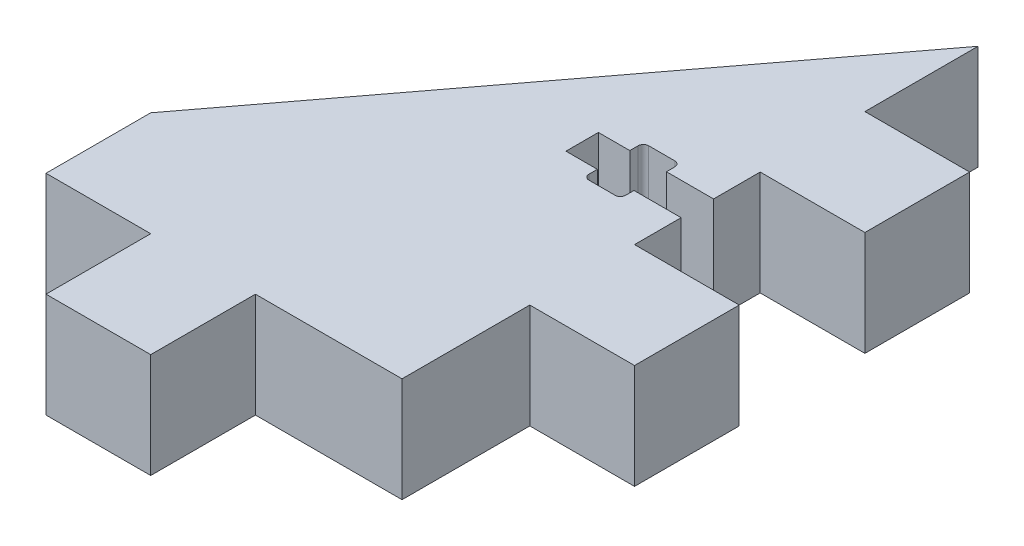
SolidWorks part; units mm, degrees
ref_plane "Front Plane" through (0, 0, 0) normal (0, 0, 1) x (1, 0, 0)
ref_plane "Top Plane" through (0, 0, 0) normal (0, 1, 0) x (1, 0, 0)
ref_plane "Right Plane" through (0, 0, 0) normal (1, 0, 0) x (0, 0, -1)
sketch "Sketch1" plane through (0, 0, 0) normal (0, 1, 0) x (1, 0, 0)
  line L0 (0, 0) -> (-14, 0)
  line L1 (-14, 0) -> (-14, -10)
  line L2 (-14, -10) -> (-24, -10)
  line L3 (-24, -10) -> (-24, 0)
  line L4 (-24, 0) -> (-34, 0)
  line L5 (-34, 0) -> (-34, 10)
  line L6 (-34, 10) -> (0, 55)
  line L7 (0, 55) -> (0, 44.2)
  line L8 (0, 44.2) -> (10, 44.2)
  line L9 (10, 44.2) -> (10, 34.2)
  line L10 (10, 34.2) -> (0, 34.2)
  line L11 (0, 34.2) -> (0, 22.2)
  line L12 (-24, 0) -> (-14, 0) construction
  line L13 (-19, 0) -> (-19, -10) construction
  line L14 (0, 17.2) -> (0, 12.2) construction
  line L15 (5, 12.2) -> (5, 21.2) construction
  line L16 (10, 34.2) -> (10, 22.2) construction
  line L17 (0, 28.2) -> (10, 28.2) construction
  line L24 (0, 22.2) -> (10, 22.2)
  line L25 (10, 22.2) -> (10, 12.2)
  line L26 (10, 12.2) -> (0, 12.2)
  line L27 (0, 12.2) -> (0, 0)
  line L32 (10, 39.2) -> (0, 39.2) construction
  line L33 (0, 39.2) -> (0, 34.2) construction
  line L34 (10, 17.2) -> (0, 17.2) construction
  line L35 (0, 17.2) -> (0, 22.2) construction
  dimension "D1" = 10
  dimension "D2" = 10
  dimension "D3" = 10
  dimension "D7" = 10
  dimension "D8" = 10
  dimension "D10" = 10
  dimension "D11" = 10
  dimension "D12" = 10
  dimension "D9" = 55
  dimension "D4" = 22
  dimension "D6" = 24
  dimension "D5" = 28.2
extrude "Boss-Extrude1" add sketch "Sketch1" along normal blind 10
sketch "Sketch2" [suppressed] plane through (0, 8, 0) normal (0, 1, 0) x (1, 0, 0)
  line L0 (0, 29.9) -> (0, 25.9) construction
  line L1 (0, 27.9) -> (-7.2, 27.9) construction
  line L2 (-7.2, 25.9) -> (-7.2, 29.9) construction
  line L3 (7.5, 36.4) -> (7.5, 20.4) construction
  line L4 (0, 36.4) -> (7.5, 36.4) construction
  line L5 (0, 27.9) -> (7.5, 27.9) construction
sketch "Sketch3" plane through (0, 10, 0) normal (0, 1, 0) x (1, 0, 0)
  line L0 (0, 28.2) -> (-11, 28.2) construction
  line L1 (0, 22.2) -> (0, 34.2) construction
  line L2 (-11, 29.75) -> (-8, 29.75)
  line L3 (-8, 29.75) -> (-8, 30.55)
  line L4 (-7.5, 31.05) -> (-5, 31.05)
  line L5 (-4.5, 30.55) -> (-4.5, 29.75)
  line L6 (-4.5, 29.75) -> (0, 29.75)
  line L7 (0, 29.75) -> (0, 26.65)
  line L8 (-11, 29.75) -> (-11, 26.65)
  line L9 (-4.5, 26.65) -> (0, 26.65)
  line L10 (-4.5, 25.85) -> (-4.5, 26.65)
  line L11 (-7.5, 25.35) -> (-5, 25.35)
  line L12 (-8, 26.65) -> (-8, 25.85)
  line L13 (-11, 26.65) -> (-8, 26.65)
  arc A0 (-8, 30.55) -> (-7.5, 31.05) centre (-7.5, 30.55) cw
  arc A1 (-5, 31.05) -> (-4.5, 30.55) centre (-5, 30.55) cw
  arc A2 (-5, 25.35) -> (-4.5, 25.85) centre (-5, 25.85) ccw
  arc A3 (-8, 25.85) -> (-7.5, 25.35) centre (-7.5, 25.85) ccw
  point P12 (-8, 31.05)
  point P15 (-4.5, 31.05)
  point P26 (-4.5, 25.35)
  point P27 (-8, 25.35)
  dimension "D7" = 0.5
  dimension "D1" = 11
  dimension "D3" = 1.55
  dimension "D2" = 8
  dimension "D4" = 3.5
  dimension "D5" = 2.85
  dimension "D6" = 1.55
extrude "Cut-Extrude1" cut sketch "Sketch3" against normal through all
equation "\"Y-ROD-SPACING\"=75"
equation "\"Y-BED-OFFSET\"=2"
equation "\"Y-BED-ROD-INSET\"=3.5"
equation "\"T-SLOT-NUT-FILLET-RADIUS\"=0.5"
equation "\"T-SLOT-SCREW-SHAFT-RADIUS\"=1.55"
equation "\"T-SLOT-SCREW-SHAFT-CUTOUT-LENGTH\"=11.0"
equation "\"T-SLOT-NUT-DEPTH\"=3.5"
equation "\"T-SLOT-NUT-WIDTH\"=2.85"
equation "\"T-SLOT-NUT-END-DISTANCE\"=8"
equation "\"ACRYLIC-TAB-CUTOUT-SIZE\"=\"ACRYLIC-THICKNESS\"+\"ACRYLIC-TAB-TOLERANCE\"*2"
equation "\"ACRYLIC-TAB-WIDTH\"=\"ACRYLIC-THICKNESS\""
equation "\"ACRYLIC-M3-HOLE\"=2.9"
equation "\"SMOOTHROD-CAP-SCREW-DISTANCE\"=20"
equation "\"FRAME-WIDTH-INNER\"=370"
equation "\"NEMA17-HOLE-SPACING\"=31"
equation "\"NEMA17-CENTRAL-CUTOUT\"=22.5"
equation "\"D3@Sketch1\"=\"ACRYLIC-TAB-WIDTH\""
equation "\"D12@Sketch1\"=\"ACRYLIC-TAB-WIDTH\""
equation "\"D2@Sketch1\"=\"ACRYLIC-TAB-WIDTH\""
equation "\"D11@Sketch1\"=\"ACRYLIC-TAB-WIDTH\""
equation "\"D1@Sketch1\"=\"ACRYLIC-TAB-WIDTH\""
equation "\"D10@Sketch1\"=\"ACRYLIC-TAB-WIDTH\""
equation "\"Z-BRACKET-REACH\"=55"
equation "\"D9@Sketch1\"=\"Z-BRACKET-REACH\""
equation "\"D6@Sketch3\"=\"T-SLOT-SCREW-SHAFT-RADIUS\""
equation "\"D3@Sketch3\"=\"T-SLOT-SCREW-SHAFT-RADIUS\""
equation "\"D4@Sketch3\"=\"T-SLOT-NUT-DEPTH\""
equation "\"D7@Sketch3\"=\"T-SLOT-NUT-FILLET-RADIUS\""
equation "\"D1@Sketch3\"=\"T-SLOT-SCREW-SHAFT-CUTOUT-LENGTH\""
equation "\"D5@Sketch3\"=\"T-SLOT-NUT-WIDTH\""
equation "\"D2@Sketch3\"=\"T-SLOT-NUT-END-DISTANCE\""
equation "\"X-ROD-SPACING\"=45"
equation "\"Z-ROD-SPACING\"=17.5"
equation "\"ACRYLIC-THICKNESS\"=10"
equation "\"ACRYLIC-THICKNESS2\"=4.5"
equation "\"TOP-BRACKET-SPACING\"=40"
equation "\"SMOOTHROD-X-LENGTH\"=350"
equation "\"SMOOTHROD-Y-LENGTH\"=350"
equation "\"SMOOTHROD-Z-LENGTH\"=350"
equation "\"SMOOTHROD-TIGHTENING-HEADROOM\"=.25"
equation "\"LEADSCREW-Z-LENGTH\"=300"
equation "\"SCREW-LENGTH-FRAME\"=\"ACRYLIC-THICKNESS\" + 10"
equation "\"SCREW-HEAD-RADIUS\"=6"
equation "\"PRINTED-X-SMOOTHROD-DIAMETER\"=9.0"
equation "\"PRINTED-X-SMOOTHROD-CUTOUT\"=10"
equation "\"PRINTED-X-BASE-HEIGHT\"=10"
equation "\"PRINTED-LM8UU-CUTOUT-SIZE\"=15.5"
equation "\"PRINTED-LM8UU-CUTOUT-LENGTH\"=24.5"
equation "\"PRINTED-X-IDLER-HEIGHT\"=16"
equation "\"PSU-MOUNTING-WIDTH\"=95"
equation "\"PSU-MOUNTING-HEIGHT\"=177"
equation "\"D1@Boss-Extrude1\"=\"ACRYLIC-THICKNESS\""
